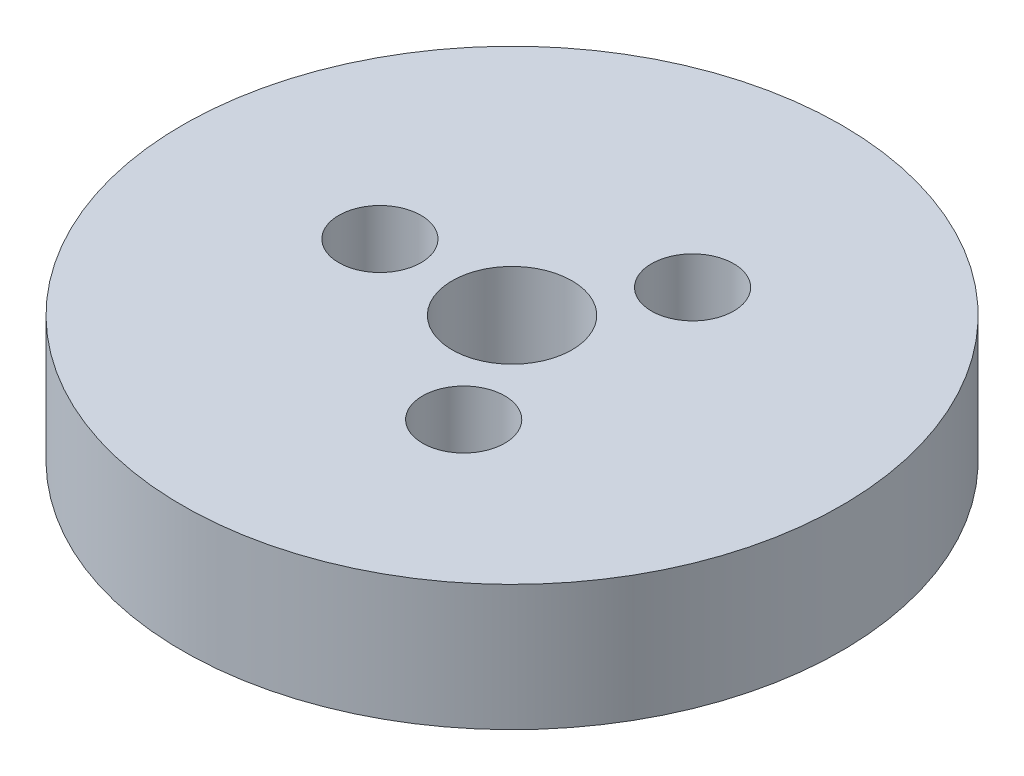
SolidWorks part; units mm, degrees
ref_plane "Front Plane" through (0, 0, 0) normal (0, 0, 1) x (1, 0, 0)
ref_plane "Top Plane" through (0, 0, 0) normal (0, 1, 0) x (1, 0, 0)
ref_plane "Right Plane" through (0, 0, 0) normal (1, 0, 0) x (0, 0, -1)
sketch "Sketch1" plane through (0, 0, 0) normal (0, 1, 0) x (1, 0, 0)
  circle A0 centre (0, 0) radius 55
  dimension "FLANGE_OD" = 110
extrude "Boss-Extrude1" add sketch "Sketch1" along normal blind 21
sketch "Sketch2" plane through (0, 0, 0) normal (0, 1, 0) x (1, 0, 0)
  circle A0 centre (0, 0) radius 10
  dimension "BORE_D" = 20
extrude "Cut-Extrude1" cut sketch "Sketch2" along normal through all
sketch "Sketch3" plane through (0, 21, 0) normal (0, 1, 0) x (1, 0, 0)
  circle A0 centre (0, 0) radius 22.0537 construction
  circle A1 centre (-22.0537, 0) radius 6.8583
  dimension "BOLT_D" = 13.7166
  dimension "BOLT_PCD" = 44.1074
extrude "Cut-Extrude2" cut sketch "Sketch3" against normal blind 15.6106
pattern_circular "CirPattern1" count 3 over 360 about axis through (0, 0, 0) along (0, 1, 0) of "Cut-Extrude2"
